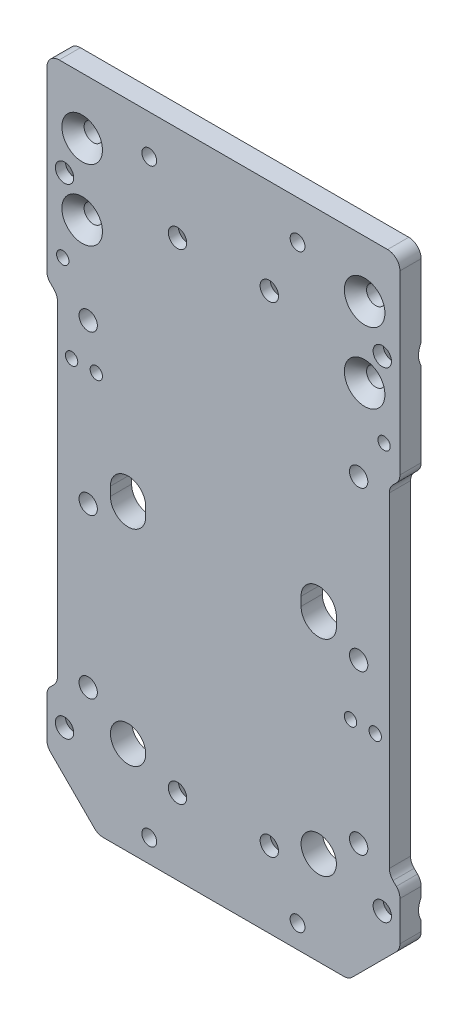
SolidWorks part; units mm, degrees
material "Polycarbonate (PC)"
ref_plane "Front Plane" through (0, 0, 0) normal (0, 0, 1) x (1, 0, 0)
ref_plane "Top Plane" through (0, 0, 0) normal (0, 1, 0) x (1, 0, 0)
ref_plane "Right Plane" through (0, 0, 0) normal (1, 0, 0) x (0, 0, -1)
sketch "Sketch1" plane through (0, 0, 0) normal (0, 0, 1) x (1, 0, 0)
  line L0 (-50, 0) -> (-35.5, -14.5)
  line L1 (-50, 0) -> (50, 0)
  line L2 (-50, 0) -> (-50, 170)
  line L3 (-50, 170) -> (50, 170)
  line L4 (50, 0) -> (50, 170)
  line L5 (-35.5, -14.5) -> (35.5, -14.5)
  line L6 (35.5, -14.5) -> (50, 0)
  line L7 (0, 0) -> (0, 178.5984) construction
  point P4 (0, 0)
  point P8 (0, -14.5)
  dimension "D1" = 100
  dimension "D3" = 14.5
  dimension "D4" = 71
  dimension "D5" = 184.5
extrude "Body" add sketch "Sketch1" along normal mid plane 6 contours L1 L4 L3 L2 | L5 L6 L1 L0 | L1 L7 L3 L2 region at (0, -6.8402, 0) region at (-25, 85, 0) region at (25, 85, 0)
sketch "Sketch6" plane through (0, 0, 3) normal (0, 0, 1) x (1, 0, 0)
  line L0 (-50, 115) -> (-47, 112)
  line L1 (0, 0) -> (0, 25.1631) construction
  line L2 (-47, 112) -> (-47, 17)
  line L3 (-47, 17) -> (-50, 14)
  line L4 (50, 115) -> (47, 112)
  line L5 (-35.5, -14.5) -> (35.5, -14.5) construction
  line L6 (47, 112) -> (47, 17)
  line L7 (47, 17) -> (50, 14)
  line L8 (-50, 115) -> (-50, 14)
  line L9 (50, 115) -> (50, 14)
  line L12 (-50, 0) -> (-50, 170) construction
  line L13 (50, 0) -> (50, 170) construction
  dimension "D1" = 94
  dimension "D2" = 28.5
  dimension "D3" = 45
  dimension "D4" = 129.5
extrude "ReduceSomeWidth" cut sketch "Sketch6" against normal through all
sketch "screwHeadHoleCarriageY" plane through (0, 0, -3) normal (0, 0, -1) x (-1, 0, 0)
  line L0 (0, 0) -> (0, 34.2129) construction
  line L1 (35.5, -14.5) -> (-35.5, -14.5) construction
  line L2 (-27, 70.2) -> (-27, 72.7) construction
  line L3 (-32, 70.2) -> (-32, 72.7)
  line L4 (-22, 70.2) -> (-22, 72.7)
  line L5 (27, 70.2) -> (27, 72.7) construction
  line L6 (22, 70.2) -> (22, 72.7)
  line L7 (32, 70.2) -> (32, 72.7)
  circle A0 centre (-27, 12) radius 5
  circle A1 centre (27, 12) radius 5
  arc A6 (-32, 70.2) -> (-22, 70.2) centre (-27, 70.2) ccw
  arc A7 (-22, 72.7) -> (-32, 72.7) centre (-27, 72.7) ccw
  arc A8 (22, 70.2) -> (32, 70.2) centre (27, 70.2) ccw
  arc A9 (32, 72.7) -> (22, 72.7) centre (27, 72.7) ccw
  point P18 (-27, 71.45)
  point P28 (27, 71.45)
  dimension "D3" = 10
  dimension "D5" = 12.5
  dimension "D1" = 54
  dimension "D2" = 26.5
  dimension "D4" = 84.7
extrude "CutForOtherScrewsHeads" cut sketch "screwHeadHoleCarriageY" against normal through all
fillet "EndMillMinimumRadius" radius 3.5 14 edges at (-50, 170, 0) (50, 170, 0) (47, 112, 0) (47, 17, 0) (-47, 17, 0) (-47, 112, 0) (-50, 14, 0) (-50, 0, 0) (-35.5, -14.5, 0) (50, 14, 0) (50, 0, 0) (35.5, -14.5, 0) (-50, 115, 0) (50, 115, 0)
hole_wizard "Ø3.5 (3.5) CableTieHoles" positions "Sketch9" profile "Sketch10" hole size "Ø3.5" standard "ANSI Metric" end condition through all
sketch "Sketch9" plane through (0, 0, -3) normal (0, 0, -1) x (-1, 0, 0)
  line L0 (-50, 116.4497) -> (-50, 166.5) construction
  line L1 (50, 116.4497) -> (50, 166.5) construction
  line L2 (34.0503, -14.5) -> (-34.0503, -14.5) construction
  point P0 (-45.5, 122)
  point P2 (45.5, 122)
  dimension "D1" = 4.5
  dimension "D2" = 4.5
  dimension "D3" = 136.5
sketch "Sketch10" plane through (45.5, 122, -3) normal (1, 0, 0) x (0, 1, 0)
  line L0 (0, 0) -> (0, 6)
  line L1 (0, 6) -> (1.75, 6)
  line L2 (1.75, 6) -> (1.75, 0)
  line L5 (1.75, 0) -> (0, 0)
  line L11 (0, -6.35) -> (0, 107.95) construction
  dimension "Thru Hole Dia." = 3.5
  dimension "Thru Hole Depth" = 6
hole_wizard "Ø4.2 (4.2) KP8 Holes1" positions "Sketch11" profile "Sketch12" hole size "Ø4.2" standard "ANSI Metric" end condition through all
sketch "Sketch11" plane through (0, 0, -3) normal (0, 0, -1) x (-1, 0, 0)
  line L0 (34.0503, -14.5) -> (-34.0503, -14.5) construction
  line L2 (0, 0) -> (0, 41.1682) construction
  point P0 (-21, 159)
  point P2 (21, 159)
  dimension "D1" = 42
  dimension "D2" = 173.5
sketch "Sketch12" plane through (21, 159, -3) normal (1, 0, 0) x (0, 1, 0)
  line L0 (0, 0) -> (0, 6)
  line L1 (0, 6) -> (2.1, 6)
  line L2 (2.1, 6) -> (2.1, 0)
  line L5 (2.1, 0) -> (0, 0)
  line L11 (0, -6.35) -> (0, 107.95) construction
  dimension "Thru Hole Dia." = 4.2
  dimension "Thru Hole Depth" = 6
hole_wizard "Ø4.2 (4.2) KP8 Holes2" positions "Sketch13" profile "Sketch14" hole size "Ø4.2" standard "ANSI Metric" end condition through all
sketch "Sketch13" plane through (0, 0, -3) normal (0, 0, -1) x (-1, 0, 0)
  line L0 (34.0503, -14.5) -> (-34.0503, -14.5) construction
  line L1 (0, 0) -> (0, 17.4832) construction
  point P0 (-21, -8)
  point P2 (21, -8)
  dimension "D1" = 42
  dimension "D2" = 6.5
sketch "Sketch14" plane through (21, -8, -3) normal (1, 0, 0) x (0, 1, 0)
  line L0 (0, 0) -> (0, 6)
  line L1 (0, 6) -> (2.1, 6)
  line L2 (2.1, 6) -> (2.1, 2.7)
  line L3 (2.1, 2.7) -> (4.8, 0)
  line L5 (4.8, 0) -> (0, 0)
  line L6 (-2.1, 2.7) -> (-4.8, 0) construction
  line L11 (0, -6.35) -> (0, 107.95) construction
  dimension "Thru Hole Dia." = 4.2
  dimension "Thru Hole Depth" = 6
  dimension "Near C'Sink Dia." = 9.6
  dimension "Near C'Sink Angle" = 90
hole_wizard "Ø5.2 (5.2) MountAngleCornerHoles" positions "Sketch15" profile "Sketch16" hole size "Ø5.2" standard "ANSI Metric" end condition through all
sketch "Sketch15" plane through (0, 0, -3) normal (0, 0, -1) x (-1, 0, 0)
  line L0 (0, 0) -> (0, 24.2214) construction
  line L2 (46.5, 170) -> (-46.5, 170) construction
  point P0 (-40, 154)
  point P2 (-40, 134)
  point P4 (40, 154)
  point P6 (40, 134)
  dimension "D1" = 80
  dimension "D2" = 20
  dimension "D3" = 16
sketch "Sketch16" plane through (40, 154, -3) normal (1, 0, 0) x (0, 1, 0)
  line L0 (0, 0) -> (0, 6)
  line L1 (0, 6) -> (5.75, 6)
  line L2 (2.6, 2.85) -> (2.6, 0)
  line L5 (2.6, 0) -> (0, 0)
  line L7 (5.75, 6) -> (2.6, 2.85)
  line L8 (-5.75, 6) -> (-2.6, 2.85) construction
  line L11 (0, -6.35) -> (0, 107.95) construction
  dimension "Thru Hole Dia." = 5.2
  dimension "Thru Hole Depth" = 6
  dimension "Far C'Sink Dia." = 11.5
  dimension "Far C'Sink Angle" = 90
hole_wizard "Ø5.2 (5.2) SK8 Mount Holes" positions "Sketch17" profile "Sketch20" hole size "Ø5.2" standard "ANSI Metric" end condition through all
sketch "Sketch17" plane through (0, 0, -3) normal (0, 0, -1) x (-1, 0, 0)
  line L0 (0, 0) -> (0, 35.1955) construction
  line L1 (34.0503, -14.5) -> (-34.0503, -14.5) construction
  point P0 (-45, 143.1)
  point P2 (-13, 143.1)
  point P4 (13, 143.1)
  point P6 (45, 143.1)
  point P8 (-45, 7)
  point P10 (-13, 7)
  point P12 (13, 7)
  point P14 (45, 7)
  dimension "D1" = 32
  dimension "D2" = 26
  dimension "D3" = 32
  dimension "D4" = 21.5
  dimension "D5" = 157.6
sketch "Sketch20" plane through (45, 143.1, -3) normal (1, 0, 0) x (0, 1, 0)
  line L0 (0, 0) -> (0, 6)
  line L1 (0, 6) -> (2.6, 6)
  line L2 (2.6, 6) -> (2.6, 3.15)
  line L3 (2.6, 3.15) -> (5.75, 0)
  line L5 (5.75, 0) -> (0, 0)
  line L6 (-2.6, 3.15) -> (-5.75, 0) construction
  line L11 (0, -6.35) -> (0, 107.95) construction
  dimension "Thru Hole Dia." = 5.2
  dimension "Thru Hole Depth" = 6
  dimension "Near C'Sink Dia." = 11.5
  dimension "Near C'Sink Angle" = 90
hole_wizard "Ø3.5 (3.5) EndSensorsHoles" positions "Sketch21" profile "Sketch22" hole size "Ø3.5" standard "ANSI Metric" end condition through all
sketch "Sketch21" plane through (0, 0, -3) normal (0, 0, -1) x (-1, 0, 0)
  line L2 (34.0503, -14.5) -> (-34.0503, -14.5) construction
  point P0 (-43, 49.5)
  point P2 (-36, 49.5)
  point P4 (36, 98.5)
  point P6 (43, 98.5)
  dimension "D1" = 7
  dimension "D2" = 7
  dimension "D3" = 72
  dimension "D4" = 64
  dimension "D5" = 113
sketch "Sketch22" plane through (43, 49.5, -3) normal (1, 0, 0) x (0, 1, 0)
  line L0 (0, 0) -> (0, 6)
  line L1 (0, 6) -> (1.75, 6)
  line L2 (1.75, 6) -> (1.75, 1.5)
  line L3 (1.75, 1.5) -> (3.25, 0)
  line L5 (3.25, 0) -> (0, 0)
  line L6 (-1.75, 1.5) -> (-3.25, 0) construction
  line L11 (0, -6.35) -> (0, 107.95) construction
  dimension "Thru Hole Dia." = 3.5
  dimension "Thru Hole Depth" = 6
  dimension "Near C'Sink Dia." = 6.5
  dimension "Near C'Sink Angle" = 90
hole_wizard "Ø5.2 (5.2) MountToBaseHoles" positions "Sketch23" profile "Sketch24" hole size "Ø5.2" standard "ANSI Metric" end condition through all
sketch "Sketch23" plane through (0, 0, 3) normal (0, 0, 1) x (1, 0, 0)
  line L0 (0, 0) -> (0, 21.7136) construction
  line L3 (-34.0503, -14.5) -> (34.0503, -14.5) construction
  point P0 (-38.3, 110.2)
  point P2 (-38.3, 65.2)
  point P4 (-38.3, 20.2)
  point P6 (38.3, 20.2)
  point P8 (38.3, 65.2)
  point P10 (38.3, 110.2)
  dimension "D1" = 76.6
  dimension "D2" = 34.7
  dimension "D3" = 124.7
  dimension "D4" = 79.7
sketch "Sketch24" plane through (-38.3, 110.2, 3) normal (1, 0, 0) x (0, -1, 0)
  line L0 (0, 0) -> (0, 6)
  line L1 (0, 6) -> (2.6, 6)
  line L2 (2.6, 6) -> (2.6, 0)
  line L5 (2.6, 0) -> (0, 0)
  line L11 (0, -6.35) -> (0, 107.95) construction
  dimension "Thru Hole Dia." = 5.2
  dimension "Thru Hole Depth" = 6
